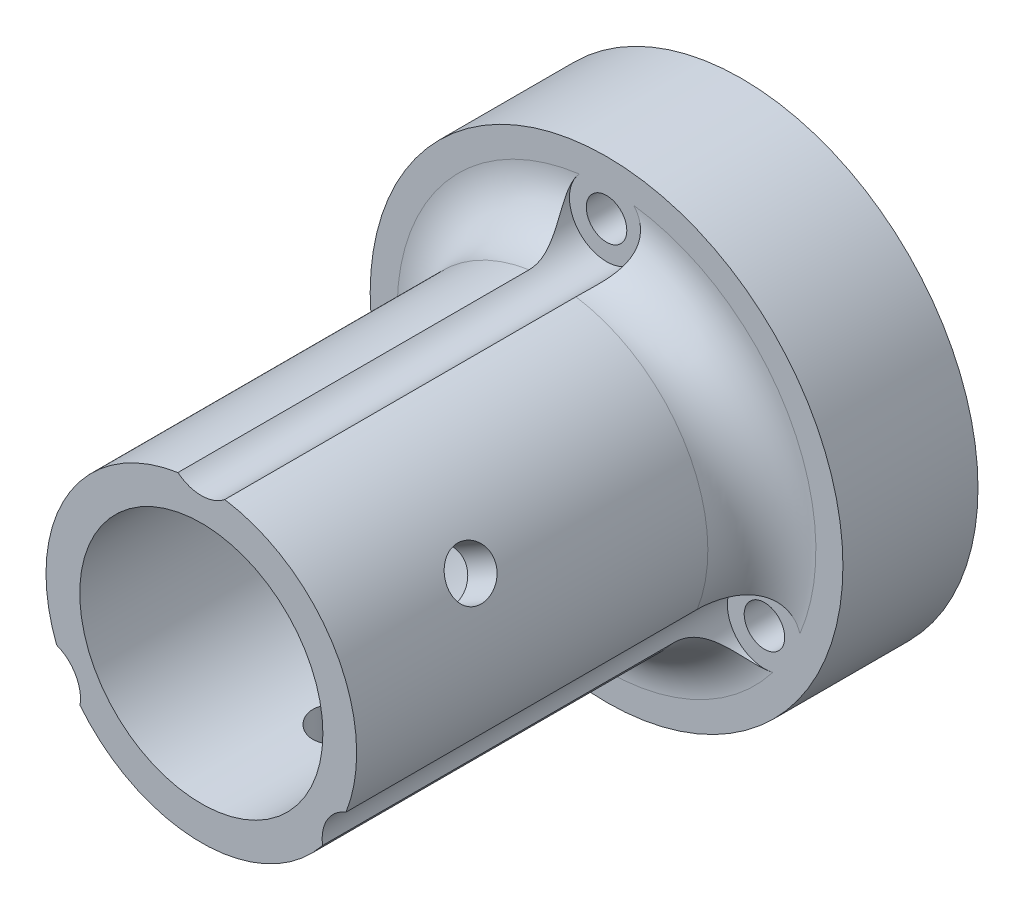
SolidWorks part; units mm, degrees
ref_plane "Front Plane" through (0, 0, 0) normal (0, 0, 1) x (1, 0, 0)
ref_plane "Top Plane" through (0, 0, 0) normal (0, 1, 0) x (1, 0, 0)
ref_plane "Right Plane" through (0, 0, 0) normal (1, 0, 0) x (0, 0, -1)
sketch "Sketch1" plane through (0, 0, 0) normal (0, 0, 1) x (1, 0, 0)
  circle A0 centre (0, 0) radius 17.5
  circle A1 centre (0, 0) radius 13.5 construction
  circle A2 centre (0, 0) radius 10
  circle A3 centre (0, 13.5) radius 1.5
  circle A4 centre (11.6913, -6.75) radius 1.5
  circle A5 centre (-11.6913, -6.75) radius 1.5
  point P13 (0, 0)
  dimension "D1" = 20
  dimension "D2" = 35
  dimension "D3" = 27
  dimension "D4" = 3
  dimension "D5" = 3
extrude "Boss-Extrude1" add sketch "Sketch1" along normal blind 10 contours A0 A5 A4 A3 A2 | A2 region at (-17.005, 0, 0)
sketch "Sketch2" plane through (0, 0, 10) normal (0, 0, 1) x (1, 0, 0)
  circle A0 centre (0, 0) radius 9
  arc A1 (10.712, -4.1837) -> (1.7328, 11.3687) centre (0, 0) ccw
  arc A2 (-1.7328, 11.3687) -> (1.7328, 11.3687) centre (0, 13.5) ccw
  arc A3 (-8.9792, -7.185) -> (-10.712, -4.1837) centre (-11.6913, -6.75) ccw
  arc A4 (10.712, -4.1837) -> (8.9792, -7.185) centre (11.6913, -6.75) ccw
  arc A5 (-8.9792, -7.185) -> (8.9792, -7.185) centre (0, 0) ccw
  arc A6 (-1.7328, 11.3687) -> (-10.712, -4.1837) centre (0, 0) ccw
  dimension "D1" = 18
  dimension "D2" = 23
extrude "Boss-Extrude2" add sketch "Sketch2" along normal blind 30
extrude "Cut-Extrude1" cut sketch "Sketch2<2>" against normal through all contours A0 region at (0, 0, 10)
sketch "Sketch2<2>" plane through (0, 0, 10) normal (0, 0, 1) x (1, 0, 0) same geometry as "Sketch2"
fillet "Fillet1" radius 4 3 edges at (-9.9593, 5.75, 10) (9.9593, 5.75, 10) (0, -11.5, 10)
ref_plane "Plane1" through (0, 0, 30) normal (0, 0, 1) x (1, 0, 0)
sketch "Sketch4" plane through (0, 0, 30) normal (0, 0, 1) x (1, 0, 0)
  line L0 (0, 0) -> (0, -21.6442) construction
  line L1 (0, 0) -> (-25.7086, 14.8428) construction
  line L2 (0, 0) -> (28.0865, 16.2158) construction
  line L3 (-6.6758, 3.8543) -> (-7.5508, 2.3388)
  line L4 (-7.5508, 2.3388) -> (-17.7335, 8.2177)
  line L5 (-17.7335, 8.2177) -> (-16.8585, 9.7333)
  line L6 (-16.8585, 9.7333) -> (-6.6758, 3.8543)
  line L7 (16.8585, 9.7333) -> (6.6758, 3.8543)
  line L8 (6.6758, 3.8543) -> (5.8008, 5.3698)
  line L9 (5.8008, 5.3698) -> (15.9835, 11.2488)
  line L10 (15.9835, 11.2488) -> (16.8585, 9.7333)
  line L11 (0, -19.4665) -> (0, -7.7086)
  line L12 (0, -7.7086) -> (1.75, -7.7086)
  line L13 (1.75, -7.7086) -> (1.75, -19.4665)
  line L14 (1.75, -19.4665) -> (0, -19.4665)
  point P19 (0, 0)
  dimension "D1" = 120
  dimension "D2" = 120
  dimension "D4" = 1.75
  dimension "D3" = 3
revolve "Cut-Revolve1" cut sketch "Sketch4" angle 360 about L1 region at (-12.2047, 6.036, 30)
revolve "Cut-Revolve2" cut sketch "Sketch4<3>" angle 360 about L2 region at (11.3297, 7.5516, 30)
sketch "Sketch4<3>" plane through (0, 0, 30) normal (0, 0, 1) x (1, 0, 0) same geometry as "Sketch4"
revolve "Cut-Revolve3" cut sketch "Sketch4<4>" angle 360 about L0 region at (0.875, -13.5876, 30)
sketch "Sketch4<4>" plane through (0, 0, 30) normal (0, 0, 1) x (1, 0, 0) same geometry as "Sketch4"
equation "\"fuse_diam\"= 0.07"
equation "\"fuse_rad\"= 0.035"
equation "\"battery_length\"= 0.076"
equation "\"battery_width\"= 0.034"
equation "\"battery_height\"= 0.051"
equation "\"bat_bay_length\"= 0.096"
equation "\"wing_shelf\"= 0.0175"
equation "\"shell\"= 0.002"
equation "\"chord_length\"= 0.089"
equation "\"tail_length\"= 0.26532000000000006"
equation "\"tail_diam\"= 0.035"
equation "\"connector\"= 0.06633000000000001"
equation "\"D2@Sketch1\"=\"fuse_rad\""
equation "\"D3@Sketch1\"=\"fuse_diam\"/2 - 0.008"
